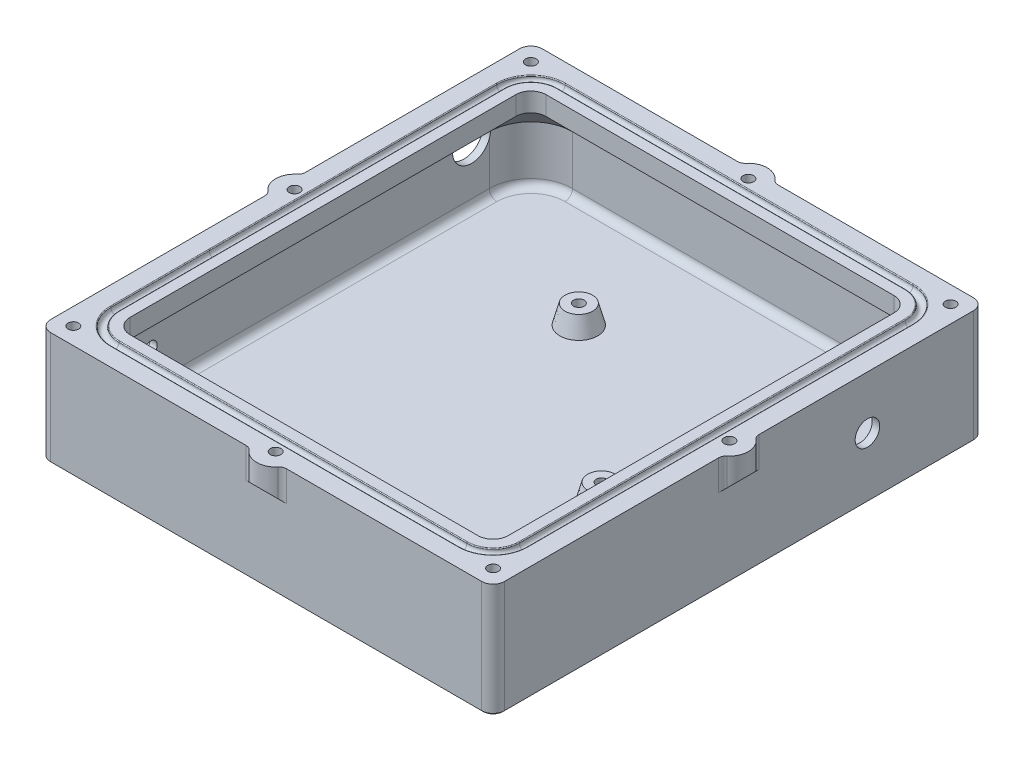
SolidWorks part; units mm, degrees
ref_plane "前视基准面" through (0, 0, 0) normal (0, 0, 1) x (1, 0, 0)
ref_plane "上视基准面" through (0, 0, 0) normal (0, 1, 0) x (1, 0, 0)
ref_plane "右视基准面" through (0, 0, 0) normal (1, 0, 0) x (0, 0, -1)
other "Configuration Table"
sketch "草图1" plane through (0, 0, 0) normal (0, 1, 0) x (1, 0, 0)
  line L1 (0, 0) -> (120, 0)
  line L2 (0, 0) -> (0, 130)
  line L3 (0, 130) -> (120, 130)
  line L4 (120, 0) -> (120, 130)
  dimension "D1" = 130
  dimension "D2" = 120
extrude "凸台-拉伸1" add sketch "草图1" along normal blind 2
sketch "草图2" plane through (0, 2, 0) normal (0, 1, 0) x (1, 0, 0)
  line L0 (0, 0) -> (120, 0) construction
  line L1 (0, 130) -> (0, 0) construction
  line L2 (120, 130) -> (0, 130) construction
  line L3 (120, 0) -> (120, 130) construction
  circle A0 centre (87.1, 61.57) radius 5
  circle A1 centre (43.1, 99.57) radius 5
  circle A2 centre (28.1, 18.57) radius 5
  point P12 (60, 130)
  point P15 (120, 65)
  point P16 (0, 65)
  point P17 (60, 0)
  dimension "D1" = 10
  dimension "D2" = 10
  dimension "D3" = 10
  dimension "D4" = 46.43
  dimension "D5" = 31.9
  dimension "D6" = 16.9
  dimension "D7" = 34.57
  dimension "D8" = 27.1
  dimension "D9" = 3.43
extrude "凸台-拉伸2" add sketch "草图2" along normal blind 5 draft 15
sketch "草图3" plane through (0, 7, 0) normal (0, 1, 0) x (1, 0, 0)
  circle A1 centre (87.1, 61.57) radius 1.4
  circle A2 centre (43.1, 99.57) radius 1.4
  circle A3 centre (28.1, 18.57) radius 1.4
  circle A4 centre (28.1, 18.57) radius 3.6603 construction
  circle A5 centre (43.1, 99.57) radius 3.6603 construction
  circle A6 centre (87.1, 61.57) radius 3.6603 construction
  dimension "D1" = 2.8
  dimension "D2" = 2.8
  dimension "D3" = 2.8
  dimension "D4" = 0
  dimension "D5" = 0
  dimension "D6" = 0
  dimension "D7" = 0
  dimension "D8" = 0
  dimension "D9" = 0
extrude "切除-拉伸1" cut sketch "草图3" against normal blind 5
sketch "草图4" plane through (0, 2, 0) normal (0, 1, 0) x (1, 0, 0)
  line L9 (2, 128) -> (2, 2)
  line L10 (2, 2) -> (118, 2)
  line L11 (118, 2) -> (118, 128)
  line L12 (118, 128) -> (2, 128)
  line L13 (2, 128) -> (2, 2)
  line L14 (2, 2) -> (118, 2)
  line L15 (118, 2) -> (118, 128)
  line L16 (118, 128) -> (2, 128)
  line L21 (0, 130) -> (0, 0)
  line L22 (0, 0) -> (120, 0)
  line L23 (120, 0) -> (120, 130)
  line L24 (120, 130) -> (0, 130)
  line L25 (0, 130) -> (0, 0)
  line L26 (0, 0) -> (120, 0)
  line L27 (120, 0) -> (120, 130)
  line L28 (120, 130) -> (0, 130)
  dimension "D1" = 2
  dimension "D2" = 0
extrude "凸台-拉伸3" add sketch "草图4" along normal blind 28
sketch "草图5" plane through (0, 30, 0) normal (0, 1, 0) x (1, 0, 0)
  line L26 (10, 120) -> (10, 10)
  line L27 (10, 10) -> (110, 10)
  line L28 (110, 10) -> (110, 120)
  line L29 (110, 120) -> (10, 120)
  line L30 (2, 2) -> (118, 2)
  line L31 (2, 128) -> (2, 2)
  line L32 (118, 128) -> (2, 128)
  line L33 (118, 2) -> (118, 128)
  line L34 (2, 2) -> (118, 2)
  line L35 (2, 128) -> (2, 2)
  line L36 (118, 128) -> (2, 128)
  line L37 (118, 2) -> (118, 128)
  dimension "D1" = 0
  dimension "D2" = 8
extrude "凸台-拉伸4" add sketch "草图5" against normal blind 5
sketch "草图9" plane through (118, 0, 0) normal (-1, 0, 0) x (0, 0, 1)
  line L1 (-130, 30) -> (0, 30) construction
  circle A0 centre (-99, 16) radius 3.25
  point P4 (-65, 30)
  dimension "D1" = 6.5
  dimension "D2" = 14
  dimension "D3" = 34
extrude "切除-拉伸4" cut sketch "草图9" against normal blind 10
sketch "草图10" plane through (2, 0, 0) normal (1, 0, 0) x (0, 0, -1)
  line L0 (28.9298, 10.6) -> (25.9298, 10.6) construction
  line L1 (23.8499, 10.6) -> (20.8499, 10.6) construction
  line L2 (21.2999, 14.1) -> (23.3999, 14.1) construction
  line L3 (28.4798, 14.1) -> (26.3798, 14.1) construction
  circle A0 centre (27.4298, 12.1) radius 1.75
  circle A1 centre (22.3499, 12.1) radius 1.75
  point P6 (27.4298, 10.6)
  point P9 (22.3499, 10.6)
  dimension "D1" = 3.5
  dimension "D2" = 3.5
  dimension "D3" = 0
  dimension "D4" = 0
  dimension "D5" = 2
  dimension "D6" = 2
extrude "切除-拉伸5" cut sketch "草图10" against normal blind 10
fillet "圆角1" radius 4 4 edges at (10, 27.5, -10) (110, 27.5, -10) (110, 27.5, -120) (10, 27.5, -120)
fillet "圆角2" radius 11 4 edges at (2, 13.5, -128) (118, 13.5, -128) (118, 13.5, -2) (2, 13.5, -2)
chamfer "倒角5" distance 8 angle 45 8 edges at (2, 25, -65) (5.2218, 25, -5.2218) (5.2218, 25, -124.7782) (60, 25, -2) (60, 25, -128) (114.7782, 25, -5.2218) (114.7782, 25, -124.7782) (118, 25, -65)
sketch "草图13" plane through (0, 30, 0) normal (0, 1, 0) x (1, 0, 0)
  line L14 (6, 6) -> (114, 6)
  line L15 (114, 6) -> (114, 124)
  line L16 (114, 124) -> (6, 124)
  line L17 (6, 124) -> (6, 6)
  line L18 (14, 6) -> (106, 6)
  line L19 (114, 14) -> (114, 116)
  line L20 (106, 124) -> (14, 124)
  line L21 (6, 116) -> (6, 14)
  arc A0 (14, 6) -> (6, 14) centre (14, 14) cw
  arc A1 (106, 6) -> (114, 14) centre (106, 14) ccw
  arc A2 (114, 116) -> (106, 124) centre (106, 116) ccw
  arc A3 (14, 124) -> (6, 116) centre (14, 116) ccw
  dimension "D2" = 8
  dimension "D1" = 6
ref_plane "基准面1" through (0, 0, -40) normal (0, 0, 1) x (1, 0, 0)
sketch "草图15" plane through (0, 0, -40) normal (0, 0, 1) x (1, 0, 0)
  line L0 (0, 30) -> (120, 30) construction
  circle A0 centre (6, 29.6) radius 1.025
  dimension "D1" = 2.05
  dimension "D2" = 0.4
sweep "切除-扫描2" cut profiles "草图15" path "草图13"
fillet "圆角4" radius 3 4 edges at (0, 15, -130) (0, 15, 0) (120, 15, 0) (120, 15, -130)
fillet "圆角5" radius 2 8 edges at (5.2218, 2, -5.2218) (2, 2, -65) (5.2218, 2, -124.7782) (60, 2, -128) (114.7782, 2, -124.7782) (118, 2, -65) (114.7782, 2, -5.2218) (60, 2, -2)
chamfer "倒角6" distance 0.4 angle 45 8 edges at (0.8787, 0, -0.8787) (60, 0, 0) (119.1213, 0, -0.8787) (120, 0, -65) (119.1213, 0, -129.1213) (60, 0, -130) (0.8787, 0, -129.1213) (0, 0, -65)
sketch "草图16" plane through (118, 0, 0) normal (-1, 0, 0) x (0, 0, 1)
  circle A0 centre (-99, 16) radius 6
  dimension "D1" = 12
extrude "切除-拉伸7" cut sketch "草图16" along normal blind 11
sketch "草图17" plane through (0, 30, 0) normal (0, 1, 0) x (1, 0, 0)
  line L0 (117, 130) -> (3, 130) construction
  line L1 (0, 127) -> (0, 3) construction
  line L2 (3, 0) -> (117, 0) construction
  line L3 (120, 3) -> (120, 127) construction
  circle A0 centre (4.5, 125.5) radius 1.4
  circle A1 centre (115.5, 125.5) radius 1.4
  circle A2 centre (115.5, 4.5) radius 1.4
  circle A3 centre (4.5, 4.5) radius 1.4
  circle A4 centre (2.5, 65) radius 1.4
  circle A5 centre (117.5, 65) radius 1.4
  circle A6 centre (60, 127.5) radius 1.4
  circle A7 centre (60, 2.5) radius 1.4
  point P20 (0, 65)
  point P23 (60, 0)
  dimension "D1" = 2.8
  dimension "D2" = 4.5
  dimension "D3" = 4.5
  dimension "D4" = 2
  dimension "D6" = 2.8
  dimension "D7" = 2.8
  dimension "D8" = 2.8
  dimension "D9" = 2.8
  dimension "D10" = 0
  dimension "D11" = 0
  dimension "D12" = 0
  dimension "D13" = 0
  dimension "D14" = 2.5
  dimension "D15" = 2.5
  dimension "D16" = 2.5
  dimension "D17" = 2.5
  dimension "D5" = 2
extrude "切除-拉伸8" cut sketch "草图17" against normal blind 5
sketch "草图18" plane through (0, 30, 0) normal (0, 1, 0) x (1, 0, 0)
  line L4 (55.6699, 130) -> (64.3301, 130)
  line L6 (120, 69.3301) -> (120, 60.6699)
  line L8 (55.6699, 0) -> (64.3301, 0)
  line L10 (0, 69.3301) -> (0, 60.6699)
  arc A0 (0, 69.3301) -> (0, 60.6699) centre (2.5, 65) ccw
  arc A1 (55.6699, 0) -> (64.3301, 0) centre (60, 2.5) ccw
  arc A2 (120, 60.6699) -> (120, 69.3301) centre (117.5, 65) ccw
  arc A3 (64.3301, 130) -> (55.6699, 130) centre (60, 127.5) ccw
  dimension "D1" = 10
  dimension "D2" = 10
  dimension "D3" = 10
  dimension "D4" = 10
extrude "凸台-拉伸5" add sketch "草图18" against normal blind 5
chamfer "倒角7" distance 3 angle 45 4 edges at (60, 25, 0) (120, 25, -65) (60, 25, -130) (0, 25, -65)
fillet "圆角6" radius 2 8 edges at (0, 26, -69.3301) (0, 26, -60.6699) (64.3301, 26, -130) (55.6699, 26, -130) (120, 26, -60.6699) (120, 26, -69.3301) (55.6699, 26, 0) (64.3301, 26, 0)
fillet "圆角7" radius 0.2 9 edges at (6.9437, 30, -78) (9.0105, 30, -120.9895) (60, 30, -123.0563) (110.9895, 30, -120.9895) (113.0563, 30, -65) (110.9895, 30, -9.0105) (60, 30, -6.9437) (9.0105, 30, -9.0105) (6.9437, 30, -27)
sketch "草图19" plane through (0, 0, 0) normal (-1, 0, 0) x (0, 0, 1)
  circle A0 centre (-112.2827, 17.1) radius 5
  circle A2 centre (-27.4298, 12.1) radius 1.75 construction
  dimension "D1" = 5
  dimension "D2" = 85
  dimension "D3" = 10
extrude "切除-拉伸9" cut sketch "草图19" against normal blind 10
